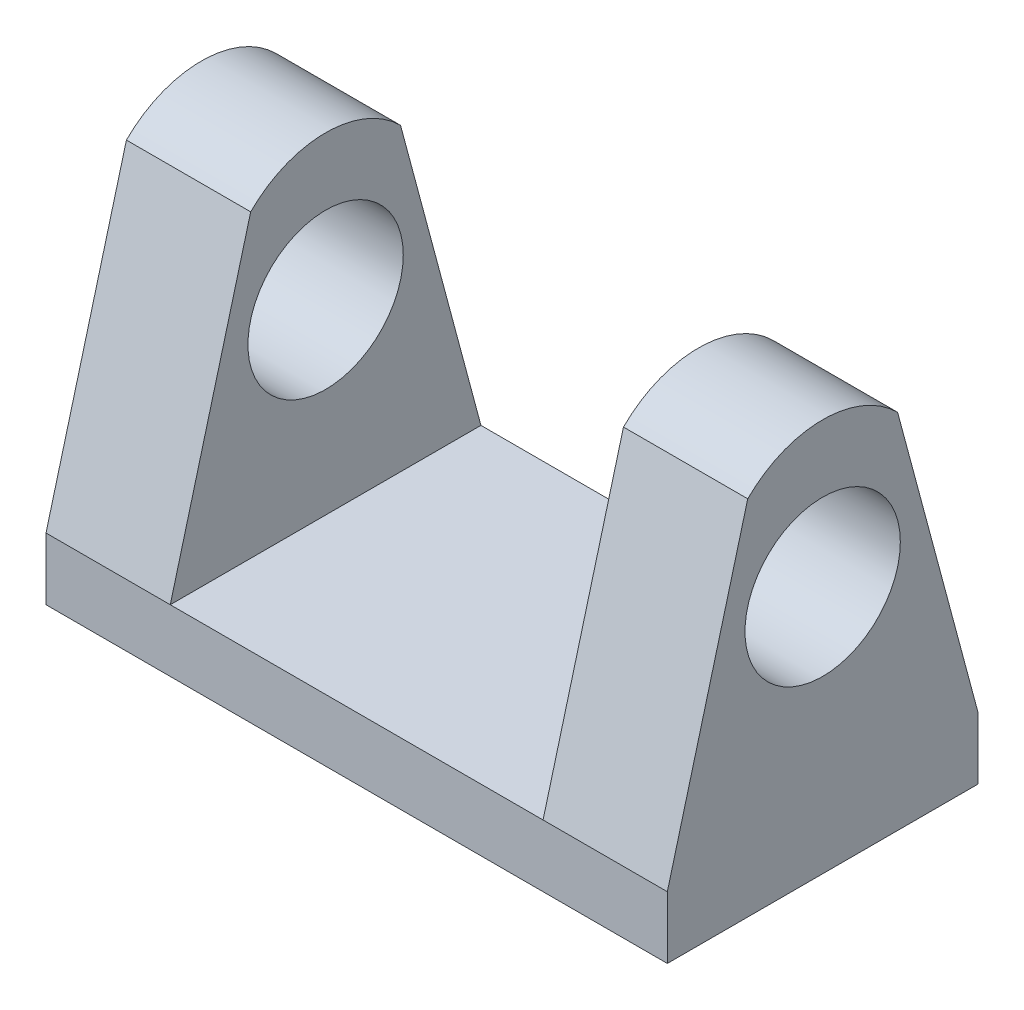
SolidWorks part; units mm, degrees
material "ABS"
ref_plane "Front Plane" through (0, 0, 0) normal (0, 0, 1) x (1, 0, 0)
ref_plane "Top Plane" through (0, 0, 0) normal (0, 1, 0) x (1, 0, 0)
ref_plane "Right Plane" through (0, 0, 0) normal (1, 0, 0) x (0, 0, -1)
sketch "Sketch1" plane through (0, 0, 0) normal (0, 1, 0) x (1, 0, 0)
  line L1 (-12.7, -6.35) -> (12.7, -6.35)
  line L2 (-12.7, -6.35) -> (-12.7, 6.35)
  line L3 (-12.7, 6.35) -> (12.7, 6.35)
  line L4 (12.7, -6.35) -> (12.7, 6.35)
  line L5 (-12.7, -6.35) -> (12.7, 6.35) construction
  line L6 (-12.7, 6.35) -> (12.7, -6.35) construction
  point P0 (0, 0)
  dimension "D1" = 25.4
  dimension "D2" = 12.7
extrude "Boss-Extrude1" add sketch "Sketch1" along normal blind 2.54
sketch "Sketch2" plane through (12.7, 0, 0) normal (1, 0, 0) x (0, 0, -1)
  line L0 (-6.35, 2.54) -> (-3.063, 14.8073)
  line L1 (6.35, 2.54) -> (3.063, 14.8073)
  line L2 (-6.35, 2.54) -> (6.35, 2.54) construction
  line L3 (-6.35, 2.54) -> (6.35, 2.54)
  arc A1 (-3.063, 14.8073) -> (3.063, 14.8073) centre (0, 11.7443) cw
  dimension "D1" = 75
  dimension "D2" = 75
extrude "Boss-Extrude2" add sketch "Sketch2" against normal blind 5.08
ref_plane "Plane1" through (0, 0, 0) normal (1, 0, 0) x (0, 0, -1)
mirror "Mirror1" about plane through (0, 0, 0) normal (1, 0, 0) of "Boss-Extrude2"
sketch "Sketch3" plane through (12.7, 0, 0) normal (1, 0, 0) x (0, 0, -1)
  line L0 (-6.35, 0) -> (6.35, 0) construction
  circle A0 centre (0, 10.16) radius 3.175
  point P2 (0, 6.2108)
  point P3 (0, 7.9339)
  point P4 (0, 9.2459)
  dimension "D1" = 10.16
extrude "Cut-Extrude1" cut sketch "Sketch3" against normal through all
